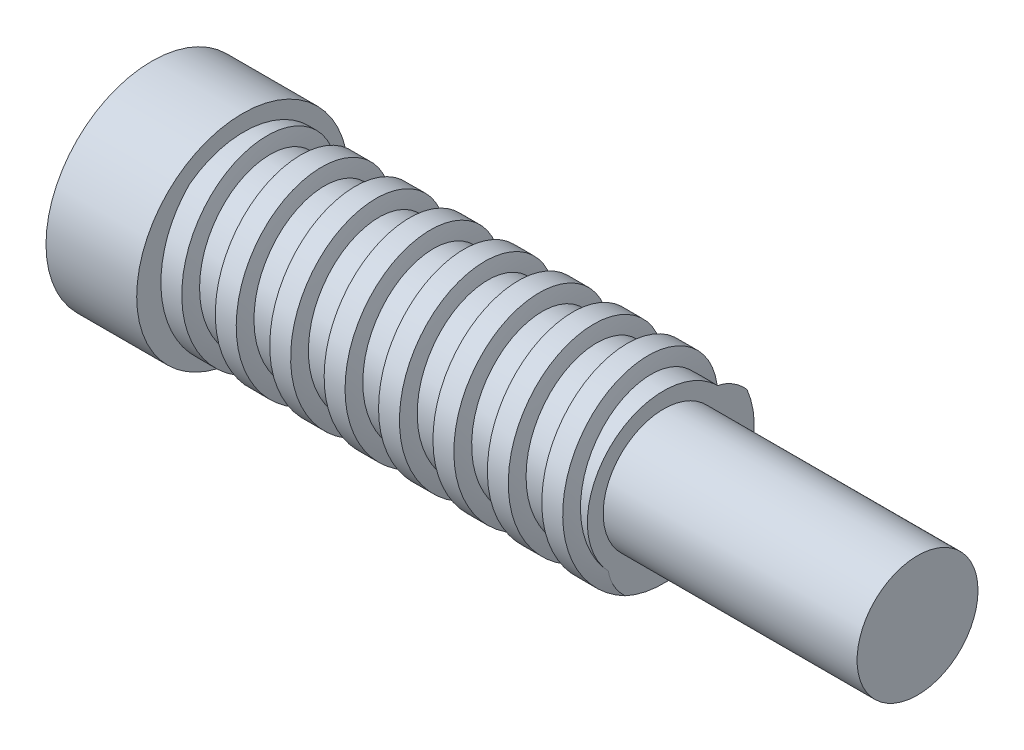
SolidWorks part; units mm, degrees
ref_plane "Piano frontale" through (0, 0, 0) normal (0, 0, 1) x (1, 0, 0)
ref_plane "Piano superiore" through (0, 0, 0) normal (0, 1, 0) x (1, 0, 0)
ref_plane "Piano destro" through (0, 0, 0) normal (1, 0, 0) x (0, 0, -1)
sketch "Schizzo1" plane through (0, 0, 0) normal (0, 0, 1) x (1, 0, 0)
  line L1 (3.0478, 1.2286) -> (21.0478, 1.2286)
  line L2 (3.0478, 1.2286) -> (3.0478, 4.2286)
  line L3 (3.0478, 4.2286) -> (21.0478, 4.2286)
  line L4 (21.0478, 1.2286) -> (21.0478, 4.2286)
  dimension "D1" = 18
  dimension "D2" = 3
revolve "Rivoluzione1" add sketch "Schizzo1" angle 360 about L1
sketch "Schizzo2" plane through (0, 0, 0) normal (0, 0, 1) x (1, 0, 0)
  line L0 (-3.0902, -11.7478) -> (-3.0902, 4.2522) construction
  line L1 (-2.5318, 4.2425) -> (1.2761, 3.1245) construction
  line L2 (-4.1212, 5.2754) -> (-2.0591, 5.2754)
  line L3 (-3.0902, -11.7478) -> (-2.5318, 4.2425) construction
  arc A2 (-2.6436, 3.7458) -> (-3.5368, 3.7458) centre (-3.0902, -11.7478) ccw
  arc A3 (-2.0591, 5.2754) -> (-2.6436, 3.7458) centre (1.2761, 3.1245) ccw
  arc A6 (-4.1212, 5.2754) -> (-3.5368, 3.7458) centre (-7.4565, 3.1245) cw
  dimension "D1" = 31
  dimension "D4" = 2
ref_plane "Piano1" through (24.0478, 0, 0) normal (1, 0, 0) x (0, 0, -1)
sketch "Schizzo3" plane through (24.0478, 0, 0) normal (1, 0, 0) x (0, 0, -1)
  circle A0 centre (0, 1.2286) radius 3 construction
  circle A1 centre (0, 1.2286) radius 3
curve "Elica/Spirale1" pitch 1.8 height 36 radius 3 centre (24.0478, 1.2286, 0) axis (-1, 0, 0) start towards (0, 0, 1)
sweep "Taglia-Sweep2" cut profiles "Schizzo2" path "Elica/Spirale1" align with end faces yes
sketch "Schizzo4" plane through (0, 0, 0) normal (0, 0, 1) x (1, 0, 0)
  line L0 (16.9301, 6.4536) -> (16.9301, -3.1913)
  line L1 (16.9301, -3.1913) -> (25.1287, -3.1913)
  line L2 (25.1287, -3.1913) -> (25.1287, 6.4536)
  line L3 (25.1287, 6.4536) -> (16.9301, 6.4536)
extrude "Taglio-Estrusione1" cut sketch "Schizzo4" along normal through all both and the other way through all
sketch "Schizzo5" plane through (0, 0, 0) normal (1, 0, 0) x (0, 0, -1)
  circle A0 centre (0, 1.2286) radius 3.5
  dimension "D1" = 7
extrude "Estrusione-Estrusione1" add sketch "Schizzo5" along normal blind 3 separate body
sketch "Schizzo6" plane through (0, 0, 0) normal (-1, 0, 0) x (0, 0, 1)
  line L1 (0, 2.7286) -> (-1.299, 1.9786)
  line L2 (-1.299, 1.9786) -> (-1.299, 0.4786)
  line L3 (-1.299, 0.4786) -> (0, -0.2714)
  line L4 (0, -0.2714) -> (1.299, 0.4786)
  line L5 (1.299, 0.4786) -> (1.299, 1.9786)
  line L6 (1.299, 1.9786) -> (0, 2.7286)
  circle A0 centre (0, 1.2286) radius 1.299 construction
  dimension "D1" = 1.5
extrude "Taglio-Estrusione2" cut sketch "Schizzo6" against normal blind 5
sketch "Schizzo7" plane through (16.9301, 0, 0) normal (1, 0, 0) x (0, 0, -1)
  circle A0 centre (0, 1.2286) radius 2
  dimension "D1" = 4
extrude "Estrusione-Estrusione2" add sketch "Schizzo7" along normal blind 8.4
ref_plane "Piano2" through (10, 0, 0) normal (-1, 0, 0) x (0, 0, 1)
sketch "Schizzo8" plane through (10, 0, 0) normal (-1, 0, 0) x (0, 0, 1)
  circle A0 centre (0, 1.2286) radius 3
  dimension "D1" = 6
